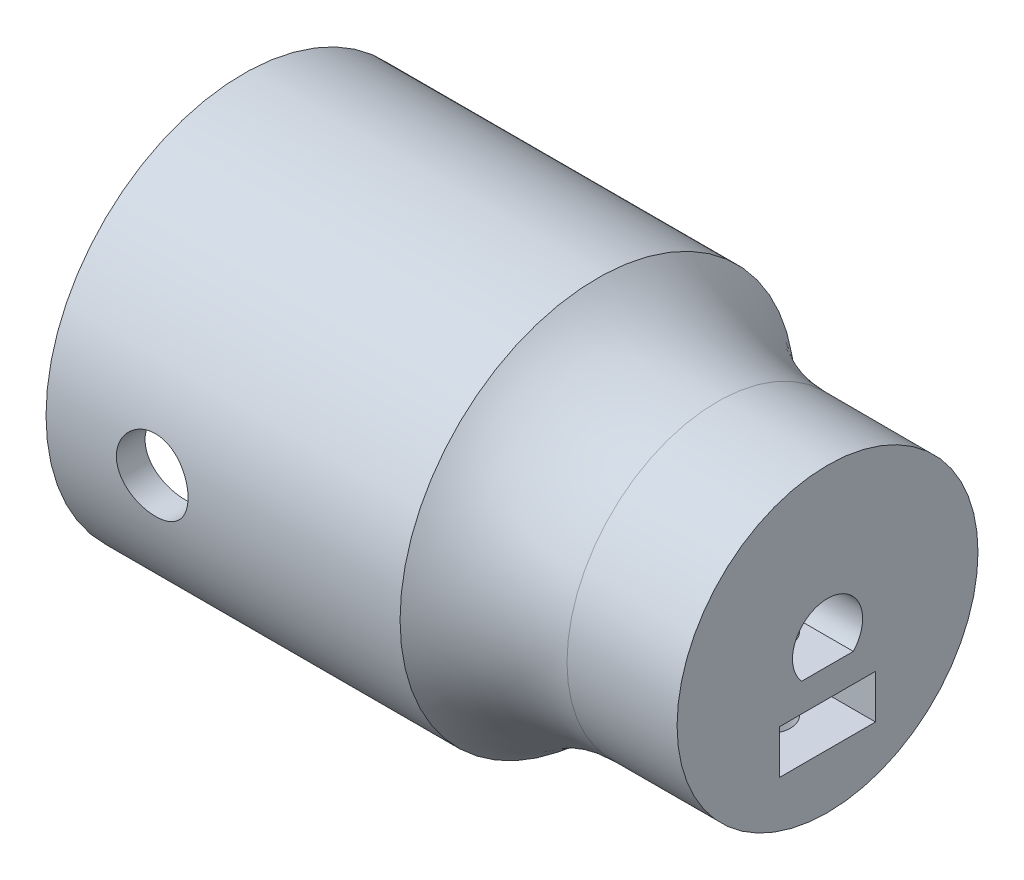
SolidWorks part; units mm, degrees
ref_plane "Alzado" through (0, 0, 0) normal (0, 0, 1) x (1, 0, 0)
ref_plane "Planta" through (0, 0, 0) normal (0, 1, 0) x (1, 0, 0)
ref_plane "Vista lateral" through (0, 0, 0) normal (1, 0, 0) x (0, 0, -1)
sketch "Croquis1" plane through (0, 0, 0) normal (1, 0, 0) x (0, 0, -1)
  line L1 (0, -6.9282) -> (6, -3.4641) construction
  line L2 (6, -3.4641) -> (6, 3.4641) construction
  line L3 (6, 3.4641) -> (0, 6.9282) construction
  line L4 (0, 6.9282) -> (-6, 3.4641) construction
  line L5 (-6, 3.4641) -> (-6, -3.4641) construction
  line L6 (-6, -3.4641) -> (0, -6.9282) construction
  circle A0 centre (0, 0) radius 6.4 construction
  circle A1 centre (0, 0) radius 6 construction
  circle A2 centre (0, 0) radius 8.5
  dimension "D2" = 12.8
  dimension "D3" = 17
  dimension "D1" = 12
extrude "Saliente-Extruir1" add sketch "Croquis1" along normal blind 30
sketch "Croquis2" plane through (30, 0, 0) normal (1, 0, 0) x (0, 0, -1)
  line L0 (-1.4311, -1.28) -> (1.4311, -1.28) construction
  line L7 (0, 0) -> (0, 1.92) construction
  line L8 (-1.4577, -1.34) -> (1.4577, -1.34)
  arc A0 (1.4311, -1.28) -> (-1.4311, -1.28) centre (0, 0) ccw construction
  arc A1 (1.4577, -1.34) -> (-1.4577, -1.34) centre (0, 0) ccw
  dimension "D1" = 3.84
  dimension "D2" = 3.2
  dimension "D3" = 0.06
extrude "Cortar-Extruir1" cut sketch "Croquis2" against normal blind 9
sketch "Croquis9" plane through (0, 0, 0) normal (-1, 0, 0) x (0, 0, 1)
  circle A0 centre (0, 0) radius 11.15
  dimension "D1" = 22.3
extrude "Saliente-Extruir5" add sketch "Croquis9" against normal blind 20
sketch "Croquis3" plane through (0, 0, 0) normal (-1, 0, 0) x (0, 0, 1)
  circle A0 centre (0, 0) radius 9.53
  dimension "D1" = 19.06
extrude "Cortar-Extruir2" cut sketch "Croquis3" against normal blind 19
sketch "Croquis5" plane through (0, 0, 0) normal (0, 0, 1) x (1, 0, 0)
  circle A0 centre (6, 0) radius 2.025
  dimension "D1" = 4.05
  dimension "D2" = 6
extrude "Cortar-Extruir4" cut sketch "Croquis5" against normal through all and the other way through all
sketch "Croquis7" plane through (30, 0, 0) normal (1, 0, 0) x (0, 0, -1)
  line L1 (-1.4577, -1.34) -> (1.4577, -1.34)
  line L2 (-1.4577, -1.34) -> (1.4577, -1.34)
  circle A0 centre (0, 0) radius 8.5 construction
  circle A1 centre (0, 0) radius 8.5
  arc A3 (1.4577, -1.34) -> (-1.4577, -1.34) centre (0, 0) ccw
  arc A4 (1.4577, -1.34) -> (-1.4577, -1.34) centre (0, 0) ccw
  dimension "D1" = 0
extrude "Saliente-Extruir3" add sketch "Croquis7" along normal blind 3
fillet "Redondeo1" radius 10 1 edges at (20, 0, 8.5)
sketch "Croquis10" plane through (33, 0, 0) normal (1, 0, 0) x (0, 0, -1)
  line L0 (-2.71, -2.94) -> (2.71, -2.94)
  line L1 (-2.65, -3) -> (2.65, -3) construction
  line L2 (-2.65, -3) -> (-2.65, -5.36) construction
  line L3 (-2.65, -5.36) -> (2.65, -5.36) construction
  line L4 (2.65, -3) -> (2.65, -5.36) construction
  line L5 (-2.65, -3) -> (2.65, -5.36) construction
  line L6 (-2.65, -5.36) -> (2.65, -3) construction
  line L7 (2.71, -2.94) -> (2.71, -5.42)
  line L8 (-2.71, -5.42) -> (2.71, -5.42)
  line L9 (-2.71, -2.94) -> (-2.71, -5.42)
  line L11 (-1.4577, -1.34) -> (1.4577, -1.34) construction
  point P4 (0, -4.18)
  dimension "D3" = 0.06
  dimension "D1" = 5.3
  dimension "D2" = 2.36
  dimension "D4" = 1.6
extrude "Cortar-Extruir5" cut sketch "Croquis10" against normal blind 6
sketch "Croquis12" plane through (0, 0, 0) normal (0, 1, 0) x (1, 0, 0)
  line L0 (33, -8.5) -> (33, 8.5) construction
  circle A0 centre (29.65, 0) radius 1.25
  dimension "D1" = 2.5
  dimension "D2" = 3.35
extrude "Cortar-Extruir6" cut sketch "Croquis12" against normal through all
equation "\"D1@Croquis3\"= 19 + \"tolerancia\""
equation "\"tolerancia\"= 0.06"
equation "\"D3@Croquis2\"=\"tolerancia\""
equation "\"D3@Croquis10\"=\"tolerancia\""
